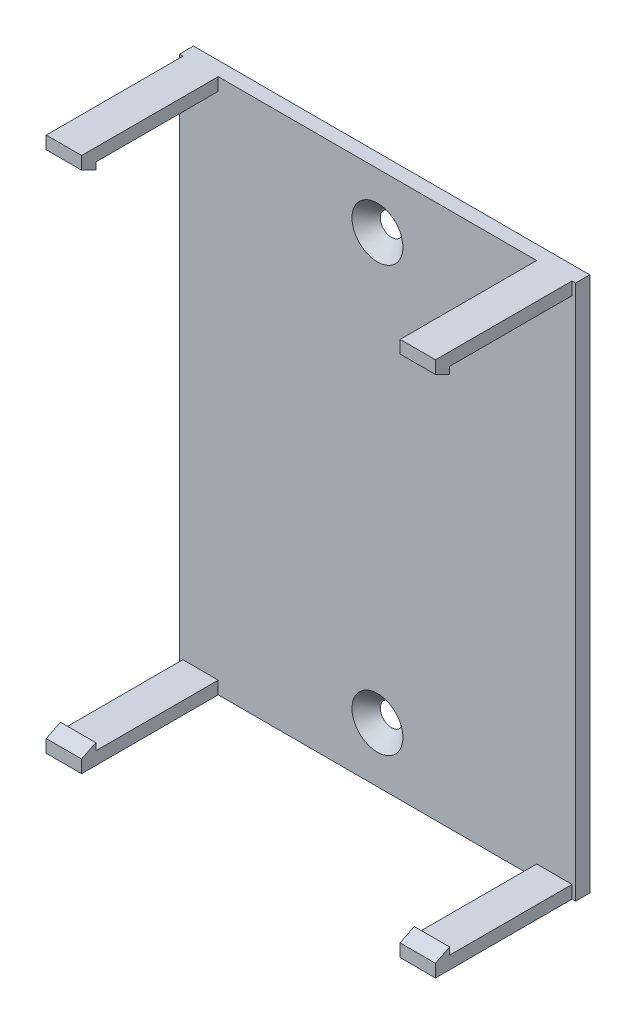
SolidWorks part; units mm, degrees
ref_plane "前视基准面" through (0, 0, 0) normal (0, 0, 1) x (1, 0, 0)
ref_plane "上视基准面" through (0, 0, 0) normal (0, 1, 0) x (1, 0, 0)
ref_plane "右视基准面" through (0, 0, 0) normal (1, 0, 0) x (0, 0, -1)
sketch "草图1" plane through (0, 0, 0) normal (0, 0, 1) x (1, 0, 0)
  line L0 (-44.2949, 0) -> (56.8787, 0) construction
  line L1 (-28, 37.825) -> (28, 37.825)
  line L2 (-28, 37.825) -> (-28, -37.825)
  line L3 (-28, -37.825) -> (28, -37.825)
  line L4 (28, 37.825) -> (28, -37.825)
  line L5 (0, 38.8839) -> (0, -47.6925) construction
  dimension "D1" = 75.65
  dimension "D2" = 56
extrude "凸台-拉伸1" add sketch "草图1" along normal blind 2
sketch "草图2" plane through (0, 0, 2) normal (0, 0, 1) x (1, 0, 0)
  line L0 (28, 37.825) -> (-28, 37.825) construction
  line L1 (-27.5, 37.825) -> (-22.5, 37.825)
  line L2 (-27.5, 37.825) -> (-27.5, 36.025)
  line L3 (-27.5, 36.025) -> (-22.5, 36.025)
  line L4 (-22.5, 37.825) -> (-22.5, 36.025)
  line L5 (-28, -37.825) -> (28, -37.825) construction
  line L6 (22.5, 36.025) -> (27.5, 36.025)
  line L7 (22.5, 36.025) -> (22.5, 37.825)
  line L8 (22.5, 37.825) -> (27.5, 37.825)
  line L9 (27.5, 36.025) -> (27.5, 37.825)
  line L10 (-27.5, -37.825) -> (-22.5, -37.825)
  line L11 (-27.5, -37.825) -> (-27.5, -36.025)
  line L12 (-27.5, -36.025) -> (-22.5, -36.025)
  line L13 (-22.5, -37.825) -> (-22.5, -36.025)
  line L14 (0, 47.7565) -> (0, -48.3412) construction
  line L15 (22.5, -37.825) -> (27.5, -37.825)
  line L16 (22.5, -37.825) -> (22.5, -36.025)
  line L17 (22.5, -36.025) -> (27.5, -36.025)
  line L18 (27.5, -37.825) -> (27.5, -36.025)
  dimension "D1" = 45
  dimension "D2" = 5
  dimension "D3" = 1.8
extrude "凸台-拉伸2" add sketch "草图2" along normal blind 19.3
sketch "草图3" plane through (-27.5, 0, 0) normal (-1, 0, 0) x (0, 0, 1)
  line L0 (21.3, 36.025) -> (19.3, 35.025)
  line L1 (19.3, 35.025) -> (19.3, 36.025)
  line L2 (21.3, 36.025) -> (2, 36.025) construction
  line L3 (19.3, 36.025) -> (21.3, 36.025)
  dimension "D1" = 1
  dimension "D2" = 2
extrude "凸台-拉伸3" add sketch "草图3" against normal up to surface (5 mm away) up to face at (-22.5, 36.7, 14.0625)
sketch "草图4" plane through (22.5, 0, 0) normal (-1, 0, 0) x (0, 0, 1)
  line L0 (19.3, 36.025) -> (19.3, 35.025)
  line L1 (19.3, 35.025) -> (21.3, 36.025)
  line L2 (21.3, 36.025) -> (19.3, 36.025)
extrude "凸台-拉伸4" add sketch "草图4" against normal up to surface (5 mm away) up to face at (27.5, 36.925, 11.65)
sketch "草图5" plane through (-27.5, 0, 0) normal (-1, 0, 0) x (0, 0, 1)
  line L0 (21.3, -36.025) -> (19.3, -35.025)
  line L1 (19.3, -35.025) -> (19.3, -36.025)
  line L2 (21.3, -36.025) -> (2, -36.025) construction
  line L3 (19.3, -36.025) -> (21.3, -36.025)
  dimension "D1" = 1
  dimension "D2" = 2
extrude "凸台-拉伸5" add sketch "草图5" against normal up to surface (5 mm away) up to face at (-22.5, -36.925, 11.65)
sketch "草图6" plane through (22.5, 0, 0) normal (-1, 0, 0) x (0, 0, 1)
  line L0 (19.3, -36.025) -> (21.3, -36.025)
  line L1 (21.3, -36.025) -> (19.3, -35.025)
  line L2 (19.3, -35.025) -> (19.3, -36.025)
extrude "凸台-拉伸6" add sketch "草图6" against normal up to surface (5 mm away) up to face at (27.5, -36.925, 11.65)
sketch "草图7" plane through (0, 0, 2) normal (0, 0, 1) x (1, 0, 0)
  line L0 (-36.2062, 0) -> (44.2069, 0) construction
  circle A0 centre (0, 30) radius 1.6
  circle A1 centre (0, -30) radius 1.6
  dimension "D2" = 3.2
  dimension "D1" = 60
extrude "切除-拉伸1" cut sketch "草图7" against normal through all
chamfer "倒角1" distance 2 angle 45 2 edges at (1.6, -30, 2) (1.6, 30, 2)
